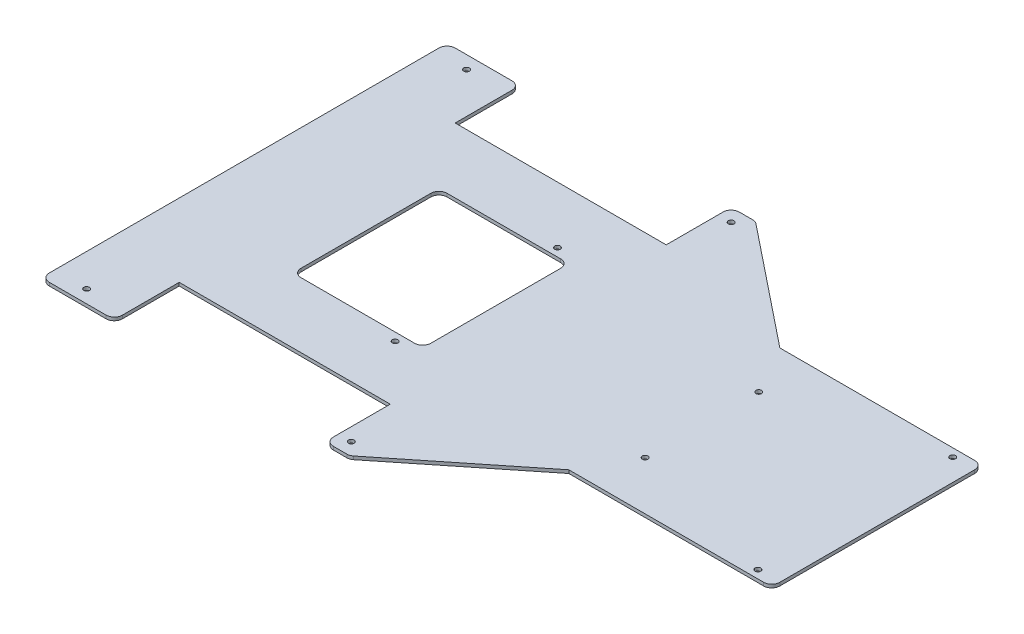
SolidWorks part; units mm, degrees
ref_plane "정면" through (0, 0, 0) normal (0, 0, 1) x (1, 0, 0)
ref_plane "윗면" through (0, 0, 0) normal (0, 1, 0) x (1, 0, 0)
ref_plane "우측면" through (0, 0, 0) normal (1, 0, 0) x (0, 0, -1)
sketch "스케치1" plane through (0, 0, 0) normal (0, 1, 0) x (1, 0, 0)
  line L1 (-195, -125) -> (195, -125)
  line L2 (-195, -125) -> (-195, 125)
  line L3 (-195, 125) -> (195, 125)
  line L4 (195, -125) -> (195, 125)
  line L5 (-195, -125) -> (195, 125) construction
  line L6 (-195, 125) -> (195, -125) construction
  point P0 (0, 0)
  dimension "D1" = 250
  dimension "D2" = 390
extrude "보스-돌출1" add sketch "스케치1" along normal blind 2
sketch "스케치2" plane through (0, 2, 0) normal (0, 1, 0) x (1, 0, 0)
  line L1 (195, 125) -> (70, 125)
  line L2 (195, 125) -> (195, 65)
  line L3 (195, 65) -> (70, 65)
  line L4 (70, 125) -> (70, 65)
  line L5 (195, -125) -> (70, -125)
  line L6 (195, -125) -> (195, -65)
  line L7 (195, -65) -> (70, -65)
  line L8 (70, -125) -> (70, -65)
  line L9 (-150, 125) -> (-20, 125)
  line L10 (-150, 125) -> (-150, 85)
  line L11 (-150, 85) -> (-20, 85)
  line L12 (-20, 125) -> (-20, 85)
  line L13 (-150, -125) -> (-20, -125)
  line L14 (-150, -125) -> (-150, -85)
  line L15 (-150, -85) -> (-20, -85)
  line L16 (-20, -125) -> (-20, -85)
  dimension "D1" = 125
  dimension "D2" = 60
  dimension "D3" = 40
  dimension "D4" = 90
  dimension "D5" = 130
extrude "컷-돌출1" cut sketch "스케치2" against normal blind 10
sketch "스케치3" plane through (0, 2, 0) normal (0, 1, 0) x (1, 0, 0)
  line L0 (-5, 125) -> (70, 65)
  line L1 (-5, -125) -> (70, -65)
  line L2 (70, -65) -> (70, -125)
  line L3 (70, -125) -> (-5, -125)
  line L4 (70, 65) -> (70, 125)
  line L5 (70, 125) -> (-5, 125)
  dimension "D1" = 75
extrude "컷-돌출2" cut sketch "스케치3" against normal blind 10
fillet "필렛1" radius 5 10 edges at (-5, 1, 125) (-5, 1, -125) (-20, 1, -125) (-20, 1, 125) (195, 1, 65) (195, 1, -65) (-150, 1, -125) (-150, 1, 125) (-195, 1, 125) (-195, 1, -125)
sketch "스케치4" plane through (0, 2, 0) normal (0, 1, 0) x (1, 0, 0)
  line L0 (-20, -85) -> (-150, -85) construction
  line L1 (-120, 45) -> (-40, 45)
  line L2 (-120, 45) -> (-120, -45)
  line L3 (-120, -45) -> (-40, -45)
  line L4 (-40, 45) -> (-40, -45)
  line L5 (-120, 45) -> (-40, -45) construction
  line L6 (-120, -45) -> (-40, 45) construction
  line L7 (-150, 85) -> (-20, 85) construction
  line L8 (-20, 85) -> (-20, 120) construction
  point P0 (-80, 0)
  dimension "D1" = 80
  dimension "D2" = 40
  dimension "D3" = 40
  dimension "D4" = 20
extrude "컷-돌출3" cut sketch "스케치4" against normal through all
fillet "필렛2" radius 5 4 edges at (-120, 1, 45) (-40, 1, 45) (-40, 1, -45) (-120, 1, -45)
sketch "스케치5" plane through (0, 2, 0) normal (0, 1, 0) x (1, 0, 0)
  line L0 (-175, 117) -> (-12, 117) construction
  line L1 (-175, 117) -> (-175, -117) construction
  line L2 (-175, -117) -> (-12, -117) construction
  line L3 (-12, 117) -> (-12, -117) construction
  line L4 (181.5, 60) -> (181.5, -60) construction
  line L5 (87, 35) -> (87, -35) construction
  line L6 (-155, 125) -> (-190, 125) construction
  line L7 (-195, 120) -> (-195, -120) construction
  line L8 (-190, -125) -> (-155, -125) construction
  line L9 (-20, 85) -> (-20, 120) construction
  line L10 (70, 65) -> (190, 65) construction
  line L11 (195, -60) -> (195, 60) construction
  line L12 (190, -65) -> (70, -65) construction
  line L13 (-52, 50) -> (-52, -50) construction
  line L14 (-150, 85) -> (-20, 85) construction
  line L15 (-20, -85) -> (-150, -85) construction
  circle A0 centre (-12, 117) radius 1.75
  circle A1 centre (-12, -117) radius 1.75
  circle A2 centre (181.5, 60) radius 1.75
  circle A3 centre (181.5, -60) radius 1.75
  circle A4 centre (-175, 117) radius 1.75
  circle A5 centre (-175, -117) radius 1.75
  circle A6 centre (87, 35) radius 1.75
  circle A7 centre (87, -35) radius 1.75
  circle A8 centre (-52, 50) radius 1.75
  circle A9 centre (-52, -50) radius 1.75
  dimension "D6" = 30
  dimension "D9" = 5
  dimension "D10" = 3.5
  dimension "D11" = 5
  dimension "D12" = 35
  dimension "D13" = 35
  dimension "D1" = 70
  dimension "D2" = 8
  dimension "D3" = 8
  dimension "D4" = 20
  dimension "D5" = 8
  dimension "D7" = 108
  dimension "D8" = 13.5
  dimension "D14" = 40
extrude "컷-돌출4" cut sketch "스케치5" against normal through all
